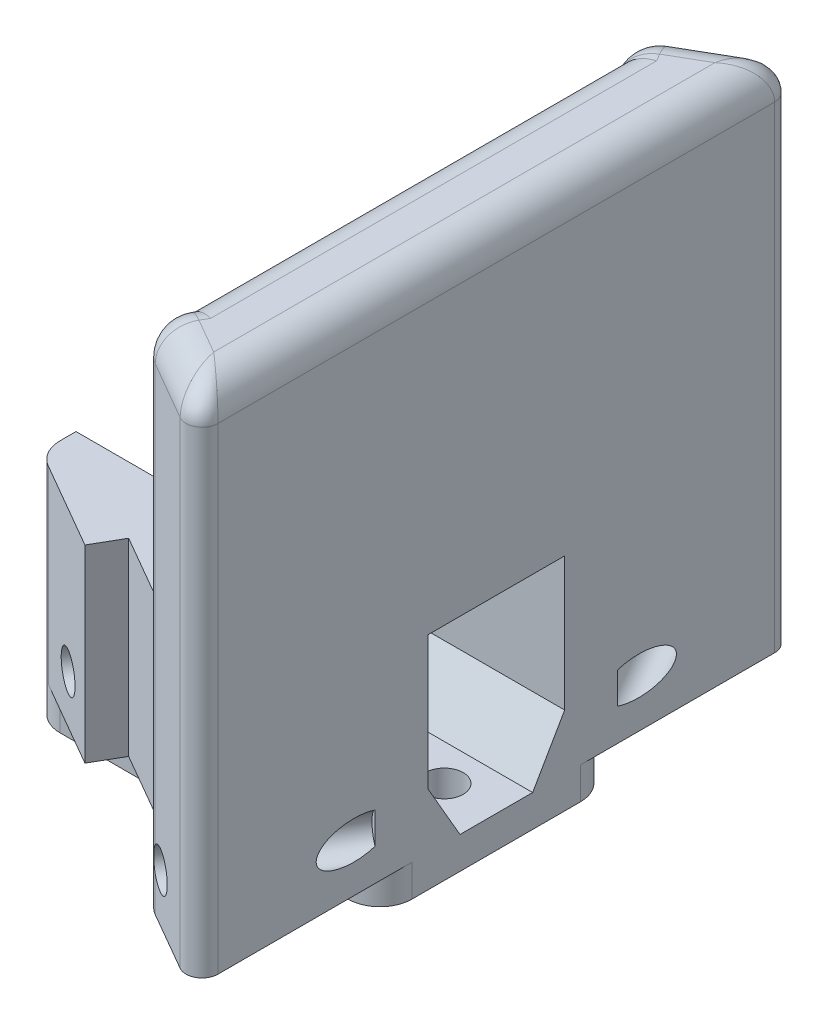
SolidWorks part; units mm, degrees
ref_plane "Front Plane" through (0, 0, 0) normal (0, 0, 1) x (1, 0, 0)
ref_plane "Top Plane" through (0, 0, 0) normal (0, 1, 0) x (1, 0, 0)
ref_plane "Right Plane" through (0, 0, 0) normal (1, 0, 0) x (0, 0, -1)
sketch "Sketch1" plane through (0, 0, 0) normal (0, 1, 0) x (1, 0, 0)
  line L0 (0, 0) -> (17.62, 0) construction
  line L1 (0, 0) -> (0, 6.35) construction
  line L2 (-2.46, 6.35) -> (20.4, 6.35)
  line L3 (-5, 3.81) -> (-5, -3.81)
  line L4 (-2.46, -6.35) -> (20.4, -6.35)
  line L5 (22.94, 3.81) -> (22.94, -3.81)
  line L6 (-5, 6.35) -> (22.94, -6.35) construction
  line L7 (-5, -6.35) -> (22.94, 6.35) construction
  line L8 (8.81, -2.8841) -> (-1.19, -2.8841) construction
  line L9 (8.81, 0) -> (8.81, -2.8841) construction
  line L10 (8.81, -2.8841) -> (18.81, -2.8841) construction
  arc A3 (20.4, -6.35) -> (22.94, -3.81) centre (20.4, -3.81) ccw
  arc A4 (20.4, 6.35) -> (22.94, 3.81) centre (20.4, 3.81) cw
  arc A5 (-5, -3.81) -> (-2.46, -6.35) centre (-2.46, -3.81) ccw
  arc A6 (-2.46, 6.35) -> (-5, 3.81) centre (-2.46, 3.81) ccw
  circle A7 centre (-1.19, -2.8841) radius 1.5
  circle A8 centre (8.81, -2.8841) radius 1.5
  circle A9 centre (18.81, -2.8841) radius 1.5
  dimension "D1" = 6.35
  dimension "D2" = 5
  dimension "D3" = 3
  dimension "D6" = 2.54
  dimension "D7" = 3.4659
  dimension "D8" = 10
  dimension "D4" = 27.94
  dimension "D5" = 12.7
  dimension "D9" = 10
  dimension "D10" = 3.81
extrude "Boss-Extrude1" add sketch "Sketch1" along normal blind 2.54
sketch "Sketch3" plane through (0, 2.54, 0) normal (0, 1, 0) x (1, 0, 0)
  line L0 (-5, 2.54) -> (22.94, 2.54)
  line L1 (-5, 3.81) -> (-5, -3.81) construction
  line L2 (22.94, -3.81) -> (22.94, 3.81) construction
  line L4 (-5, 3.81) -> (-5, 2.54)
  line L5 (22.94, 2.54) -> (22.94, 3.81)
  line L7 (0, 0) -> (20, 0) construction
  line L8 (20.4, -6.35) -> (-2.46, -6.35) construction
  line L9 (22.94, -2.54) -> (22.94, -3.81) construction
  line L10 (-5, -3.81) -> (-5, -2.54) construction
  line L11 (-5, -2.54) -> (22.94, -2.54) construction
  line L12 (22.94, 3.81) -> (22.94, 19.2079)
  line L13 (21.035, 20.3078) -> (-3.73, 6.0097)
  line L14 (20.4, 6.35) -> (-2.46, 6.35) construction
  arc A0 (22.94, 3.81) -> (20.4, 6.35) centre (20.4, 3.81) ccw construction
  arc A1 (-2.46, 6.35) -> (-5, 3.81) centre (-2.46, 3.81) ccw construction
  arc A3 (-3.73, 6.0097) -> (-5, 3.81) centre (-2.46, 3.81) ccw
  arc A4 (-2.46, -6.35) -> (-5, -3.81) centre (-2.46, -3.81) cw construction
  arc A5 (22.94, -3.81) -> (20.4, -6.35) centre (20.4, -3.81) cw construction
  arc A6 (22.94, 19.2079) -> (21.035, 20.3078) centre (21.67, 19.2079) ccw
  dimension "0.01" = 1.27
  dimension "D1" = 2.54
  dimension "D2" = 30
extrude "Boss-Extrude3" add sketch "Sketch3" along normal blind 15
sketch "Sketch5" plane through (-5.8604, 0, -4.7797) normal (0.5, 0, 0.866) x (0.866, 0, -0.5)
  line L0 (16.7581, 17.54) -> (16.7581, 0) construction
  line L1 (-4.2529, 17.54) -> (37.7691, 17.54) construction
  line L2 (23.5273, 0) -> (3.73, 0) construction
  line L3 (16.7581, 6.35) -> (6.7581, 6.35) construction
  line L4 (-0.3747, 17.54) -> (23.822, 17.54) construction
  line L5 (31.0562, 17.54) -> (2.46, 17.54) construction
  line L6 (2.46, 17.54) -> (0.2603, 17.54) construction
  circle A0 centre (6.7581, 6.35) radius 1.5
  circle A1 centre (26.7581, 6.35) radius 1.5
  dimension "D1" = 3
  dimension "D2" = 10
  dimension "D3" = 6.35
  dimension "D4" = 17.54
extrude "Cut-Extrude1" cut sketch "Sketch5" along normal blind 12.7
chamfer "Chamfer1" distance 2.54 angle 60 1 edges at (8.97, 2.54, -2.54) first distance on face at (8.97, 2.54, 2.7154)
sketch "Sketch11" plane through (0, 17.54, 0) normal (0, 1, 0) x (1, 0, 0)
  line L0 (3.1532, 9.9837) -> (4.4232, 7.784)
  line L1 (21.035, 20.3078) -> (-3.73, 6.0097) construction
  line L2 (4.4232, 7.784) -> (15.4218, 14.134)
  line L3 (15.4218, 14.134) -> (14.1518, 16.3337)
  line L4 (14.1518, 16.3337) -> (3.1532, 9.9837)
  point P7 (8.6525, 13.1587)
  dimension "D1" = 2.54
  dimension "D2" = 12.7
extrude "Cut-Extrude5" cut sketch "Sketch11" against normal through all both and the other way through all
sketch "Sketch12" plane through (0, 2.54, 0) normal (0, 1, 0) x (1, 0, 0)
  line L0 (7.31, -2.8841) -> (20.31, -2.8841) construction
  circle A0 centre (8.81, -2.8841) radius 1.5 construction
  circle A1 centre (18.81, -2.8841) radius 1.5 construction
ref_plane "Plane1" through (0, 0, 2.8841) normal (0, 0, 1) x (1, 0, 0)
mirror "Mirror1" about plane through (0, 0, 2.8841) normal (0, 0, 1) of "Cut-Extrude5", "Boss-Extrude1", "Boss-Extrude3", "Cut-Extrude1", "Chamfer1"
sketch "Sketch6" plane through (0, 17.54, 0) normal (0, 1, 0) x (1, 0, 0)
  line L0 (-7.027, -2.8841) -> (27.2796, -2.8841)
  line L1 (-3.4925, -2.8841) -> (3.4925, -2.8841) construction
  line L2 (27.2796, -2.8841) -> (27.2796, 23.1072)
  line L3 (27.2796, 23.1072) -> (-7.027, 23.1072)
  line L4 (-7.027, 23.1072) -> (-7.027, -2.8841)
extrude "Cut-Extrude2" [suppressed] cut sketch "Sketch6" against normal through all both and the other way through all
sketch "Sketch7" [suppressed] plane through (0, 0, 0) normal (0, 1, 0) x (1, 0, 0)
  line L0 (-6.35, 0) -> (6.35, 0) construction
  line L1 (-6.35, 6.35) -> (6.35, 6.35)
  line L3 (0, 0) -> (0, -46.575) construction
  line L4 (6.35, -6.35) -> (6.35, -28.575)
  line L5 (6.35, -28.575) -> (15, -28.575)
  line L6 (15, -28.575) -> (15, -46.575)
  line L7 (15, -46.575) -> (-15, -46.575)
  line L8 (-15, -28.575) -> (-15, -46.575)
  line L9 (-6.35, -28.575) -> (-15, -28.575)
  line L10 (-6.35, -6.35) -> (-6.35, -28.575)
  arc A0 (-6.35, 6.35) -> (-6.35, -6.35) centre (-6.35, 0) ccw
  arc A1 (6.35, -6.35) -> (6.35, 6.35) centre (6.35, 0) ccw
  circle A2 centre (6.35, 0) radius 1.75
  circle A3 centre (-6.35, 0) radius 1.75
  point P2 (0, 0)
  dimension "D2" = 6.35
  dimension "D3" = 3.5
  dimension "D1" = 12.7
  dimension "D4" = 30
  dimension "D5" = 18
  dimension "D6" = 28.575
extrude "Boss-Extrude4" [suppressed] add sketch "Sketch7" along normal blind 10.16
sketch "Sketch8" [suppressed] plane through (0, 10.16, 0) normal (0, 1, 0) x (1, 0, 0)
  line L0 (6.35, -6.35) -> (-6.35, -6.35)
  line L8 (-6.35, -6.35) -> (-6.35, -28.575)
  line L9 (-6.35, -28.575) -> (-15, -28.575)
  line L10 (-15, -28.575) -> (-15, -46.575)
  line L11 (-15, -46.575) -> (15, -46.575)
  line L12 (15, -46.575) -> (15, -28.575)
  line L13 (15, -28.575) -> (6.35, -28.575)
  line L14 (6.35, -28.575) -> (6.35, -6.35)
  line L15 (6.35, 6.35) -> (-6.35, 6.35)
  line L16 (-6.35, -6.35) -> (-6.35, -28.575)
  line L17 (-6.35, -28.575) -> (-15, -28.575)
  line L18 (-15, -28.575) -> (-15, -46.575)
  line L19 (-15, -46.575) -> (15, -46.575)
  line L20 (15, -46.575) -> (15, -28.575)
  line L21 (15, -28.575) -> (6.35, -28.575)
  line L22 (6.35, -28.575) -> (6.35, -6.35)
  arc A2 (-6.35, 6.35) -> (-6.35, -6.35) centre (-6.35, 0) ccw
  arc A3 (6.35, -6.35) -> (6.35, 6.35) centre (6.35, 0) ccw
  dimension "D1" = 0
extrude "Boss-Extrude5" [suppressed] add sketch "Sketch8" along normal blind 25.4
fillet "Fillet1" [suppressed] radius 2.54
sketch "Sketch9" [suppressed] plane through (0, 35.56, 0) normal (0, 1, 0) x (1, 0, 0)
  line L0 (0, -6.35) -> (0, -46.575) construction
  line L1 (3.81, -6.35) -> (-3.81, -6.35) construction
  line L2 (-12.46, -46.575) -> (12.46, -46.575) construction
  line L3 (-10, -41.575) -> (0, -41.575) construction
  circle A0 centre (-10, -41.575) radius 1.5
  circle A1 centre (10, -41.575) radius 1.5
  dimension "D2" = 3
  dimension "D1" = 5
  dimension "D3" = 10
extrude "Cut-Extrude3" [suppressed] cut sketch "Sketch9" against normal through all both and the other way through all
sketch "Sketch10" [suppressed] plane through (0, 0, 46.575) normal (0, 0, 1) x (1, 0, 0)
  line L0 (0, 0) -> (0, 35.56) construction
  line L1 (-12.46, 35.56) -> (12.46, 35.56) construction
  line L3 (-7.62, 35.56) -> (7.62, 35.56)
  line L4 (-7.62, 35.56) -> (-7.62, 10.16)
  line L5 (-7.62, 10.16) -> (7.62, 10.16)
  line L6 (7.62, 35.56) -> (7.62, 10.16)
  line L7 (-7.62, 35.56) -> (7.62, 10.16) construction
  line L8 (-7.62, 10.16) -> (7.62, 35.56) construction
  line L9 (3.81, 10.16) -> (-3.81, 10.16) construction
  point P5 (0, 22.86)
  dimension "D1" = 15.24
extrude "Cut-Extrude4" [suppressed] cut sketch "Sketch10" against normal through all both and the other way through all
sketch "Sketch13" plane through (0, 17.54, 0) normal (0, 1, 0) x (1, 0, 0)
  line L9 (15.4218, -19.9023) -> (14.1518, -22.102) construction
  line L10 (14.1518, -22.102) -> (21.035, -26.0761) construction
  line L11 (22.94, -24.9762) -> (22.94, -8.3083) construction
  line L14 (14.1518, 16.3337) -> (15.4218, 14.134) construction
  line L20 (22.94, 2.54) -> (22.94, 19.2079) construction
  line L21 (21.035, 20.3078) -> (14.1518, 16.3337) construction
  line L25 (15.4218, -19.9023) -> (14.1518, -22.102)
  line L26 (14.1518, -22.102) -> (21.035, -26.0761)
  line L27 (22.94, -24.9762) -> (22.94, -8.3083)
  line L30 (14.1518, 16.3337) -> (15.4218, 14.134)
  line L36 (22.94, 2.54) -> (22.94, 19.2079)
  line L37 (21.035, 20.3078) -> (14.1518, 16.3337)
  line L38 (15.4218, 14.134) -> (15.4218, -19.9023)
  line L39 (22.94, 2.54) -> (22.94, -8.3083)
  arc A0 (21.035, -26.0761) -> (22.94, -24.9762) centre (21.67, -24.9762) ccw construction
  arc A3 (22.94, 19.2079) -> (21.035, 20.3078) centre (21.67, 19.2079) ccw construction
  arc A4 (21.035, -26.0761) -> (22.94, -24.9762) centre (21.67, -24.9762) ccw
  arc A7 (22.94, 19.2079) -> (21.035, 20.3078) centre (21.67, 19.2079) ccw
extrude "Boss-Extrude6" add sketch "Sketch13" along normal blind 25.4
fillet "Fillet3" radius 2.54 8 edges at (17.5934, 42.94, 24.0891) (22.305, 42.94, 26.0761) (17.5934, 42.94, -18.3208) (22.305, 42.94, -20.3078) (14.7868, 42.94, -15.2339) (14.7868, 42.94, 21.0022) (15.4218, 42.94, 2.8841) (22.94, 42.94, 2.8841)
fillet "Fillet4" radius 2.54 4 edges at (15.168, 42.1961, 21.8297) (15.168, 42.1961, -16.0614) (14.1518, 21.47, 22.102) (14.1518, 21.47, -16.3337)
